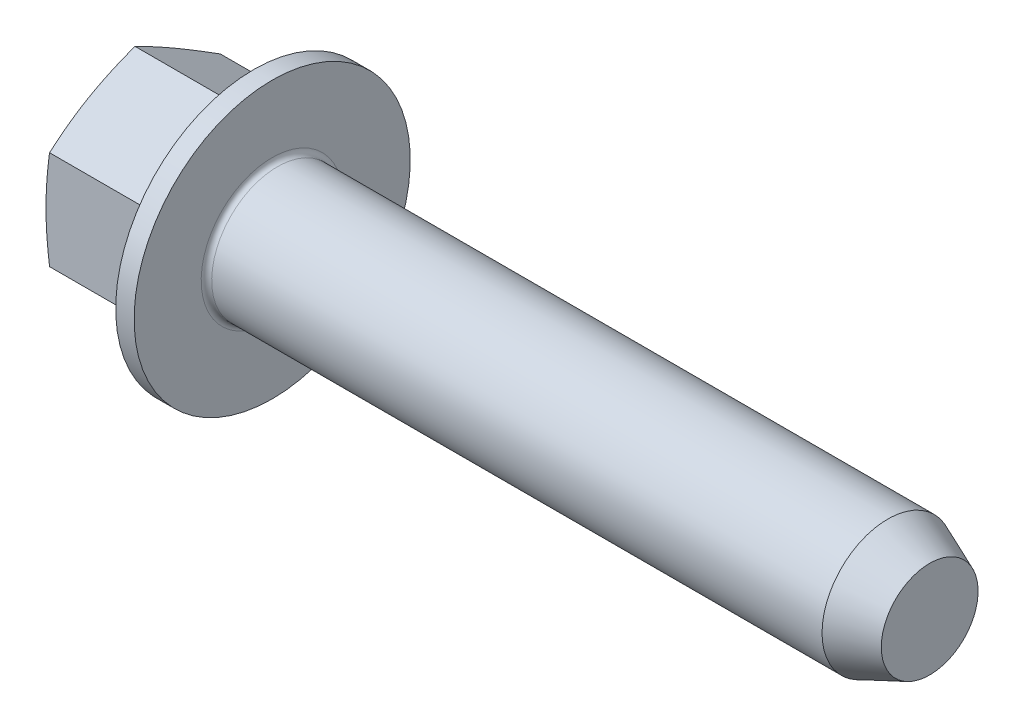
SolidWorks part; units mm, degrees
ref_plane "Front Plane" through (0, 0, 0) normal (0, 0, 1) x (1, 0, 0)
ref_plane "Top Plane" through (0, 0, 0) normal (0, 1, 0) x (1, 0, 0)
ref_plane "Right Plane" through (0, 0, 0) normal (1, 0, 0) x (0, 0, -1)
other "Configuration Table"
sketch "Sketch1" plane through (0, 0, 0) normal (0, 0, 1) x (1, 0, 0)
  line L0 (0, 0) -> (50, 0) construction
  line L1 (0, 0) -> (-10.7, 0) construction
  line L2 (0.4, 5) -> (49.172, 5)
  line L3 (50, 0) -> (50, 4.172)
  line L4 (0, 5.4) -> (0, 10.5)
  line L5 (0, 10.5) -> (-1.4, 10.5)
  line L6 (-1.4, 10.5) -> (-2.4718, 6.5)
  line L7 (-2.4718, 6.5) -> (-10.7, 6.5)
  line L8 (-10.7, 6.5) -> (-10.7, 5.2)
  line L9 (-10.7, 5.2) -> (-9.3625, 5.2)
  line L10 (-9.3625, 5.2) -> (-9.3625, 0)
  line L11 (-9.3625, 0) -> (50, 0)
  line L12 (-9.3625, 0) -> (-9.3625, 5.58) construction
  line L14 (50, 4.172) -> (49.172, 5)
  line L15 (50, 0) -> (1.5, 0) construction
  arc A0 (0.4, 5) -> (0, 5.4) centre (0.4, 5.4) cw
  dimension "D7" = 0.4
  dimension "L" = 50
  dimension "K" = 10.7
  dimension "s" = 13
  dimension "dia" = 10
  dimension "D1" = 10.4
  dimension "D2" = 1.3375
  dimension "c" = 1.4
  dimension "D4" = 15
  dimension "D5" = 45
  dimension "min" = 8.344
  dimension "B" = 48.5
  dimension "Dc" = 21
revolve "Revolve1" add sketch "Sketch1" angle 360 about L11
cosmetic thread "Cosmetic Thread1" [suppressed] parameters "D1"=47.272, "D2"=8.344
sketch "Sketch2" plane through (-10.7, 0, 0) normal (-1, 0, 0) x (0, 0, 1)
  line L1 (0, 7.5056) -> (-6.5, 3.7528)
  line L2 (-6.5, 3.7528) -> (-6.5, -3.7528)
  line L3 (-6.5, -3.7528) -> (0, -7.5056)
  line L4 (0, -7.5056) -> (6.5, -3.7528)
  line L5 (6.5, -3.7528) -> (6.5, 3.7528)
  line L6 (6.5, 3.7528) -> (0, 7.5056)
  circle A0 centre (0, 0) radius 5.2 construction
  circle A1 centre (0, 0) radius 5.2
  circle A2 centre (0, 0) radius 6.5 construction
  circle A3 centre (0, 0) radius 6.5 construction
extrude "Extrude1" add sketch "Sketch2" against normal up to next (10.7 mm away)
sketch "Sketch3" plane through (0, 0, 0) normal (0, 1, 0) x (1, 0, 0)
  line L0 (-11.5708, 3.25) -> (-9.8292, 9.75)
  line L1 (-10.7, 0) -> (-10.7, 6.5) construction
  line L2 (0, 0) -> (-3.6033, 0) construction
  line L3 (-9.8292, 9.75) -> (-11.5708, 9.75)
  line L4 (-11.5708, 9.75) -> (-11.5708, 3.25)
  dimension "D1" = 15
  dimension "D2" = 6.5
revolve "Cut-Revolve1" cut sketch "Sketch3" angle 360 about L2
fillet "Fillet1" radius 0.6 6 edges
sketch "Sketch4" plane through (0, 0, 0) normal (0, 0, 1) x (1, 0, 0)
  line L0 (0, 0) -> (5.3731, 0) construction
  line L1 (50, -4.172) -> (50, 4.172) construction
  line L3 (50, 3.68) -> (46.8132, 5)
  line L4 (0.4, 5) -> (49.172, 5) construction
  line L5 (46.8132, 5) -> (46.8132, 5.5)
  line L6 (46.8132, 5.5) -> (50, 5.5)
  line L7 (50, 5.5) -> (50, 3.68)
  dimension "D1" = 0.5
  dimension "D2" = 22.5
  dimension "Dp" = 7.36
revolve "Cut-Revolve2" cut sketch "Sketch4" angle 360 about L0
sketch "Sketch5" plane through (0, 0, 0) normal (0, 0, 1) x (1, 0, 0)
  line L0 (50, 0) -> (2.728, 0) construction
  line L1 (-9.3625, 0) -> (50, 0) construction
  line L2 (3.206, 4.172) -> (3.6841, 5)
  line L3 (3.6841, 5) -> (3.6841, 5.9561)
  line L4 (3.6841, 5.9561) -> (2.728, 5.9561)
  line L5 (2.728, 5.9561) -> (2.728, 5)
  line L6 (2.728, 5) -> (3.206, 4.172)
  dimension "B" = 47.272
  dimension "D1" = 8.344
  dimension "D2" = 10
revolve "Cut-Revolve10" [suppressed] cut sketch "Sketch5" angle 360 about L0
pattern_linear "LPattern10" [suppressed] count 32 spacing 1.5 along (1, 0, 0) of bodies 111
equation "\"D1@Sketch1\" = \"s@Sketch1\" / 10 * 8"
equation "\"D2@Sketch1\" = \"K@Sketch1\" / 8"
equation "\"D2@Sketch3\" = \"s@Sketch1\" / 2"
equation "\"D2@Cosmetic Thread1\" = \"min@Sketch1\""
equation "\"D1@Cosmetic Thread1\" = \"B@Sketch1\" -  ( \"dia@Sketch1\" - \"min@Sketch1\" )  / 2 - \"D7@Sketch1\""
equation "\"D1@Sketch5\" = \"D2@Cosmetic Thread1\""
equation "\"D2@Sketch5\" = \"dia@Sketch1\""
equation "\"B@Sketch5\" = \"D1@Cosmetic Thread1\""
equation "\"D1@LPattern10\" = int( \"D1@Cosmetic Thread1\" / \"D3@LPattern10\" + 0.999 ) "
